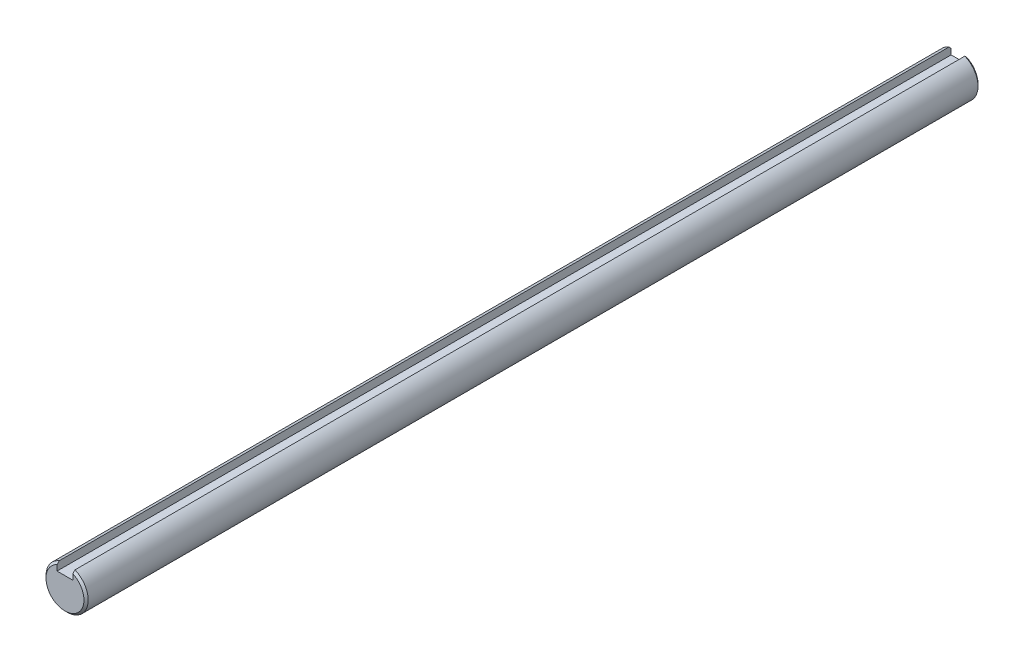
SolidWorks part; units mm, degrees
ref_plane "Front Plane" through (0, 0, 0) normal (0, 0, 1) x (1, 0, 0)
ref_plane "Top Plane" through (0, 0, 0) normal (0, 1, 0) x (1, 0, 0)
ref_plane "Right Plane" through (0, 0, 0) normal (1, 0, 0) x (0, 0, -1)
sketch "Sketch1" plane through (0, 0, 0) normal (0, 0, 1) x (1, 0, 0)
  line L0 (-2.2451, -2.2451) -> (-1.1225, -1.1225) construction
  line L1 (3.4925, 0) -> (-3.4925, 0) construction
  line L2 (0, 0) -> (0, 3.175) construction
  line L4 (-1.1906, 3.175) -> (1.1906, 3.175) construction
  line L5 (-1.1906, 3.175) -> (-1.1906, 1.7527) construction
  line L6 (-1.1906, 1.7527) -> (1.1906, 1.7527) construction
  line L7 (1.1906, 3.175) -> (1.1906, 1.7527) construction
  line L8 (-1.1906, 3.175) -> (1.1906, 1.7527) construction
  line L9 (-1.1906, 1.7527) -> (1.1906, 3.175) construction
  circle A0 centre (0, 0) radius 1.5875 construction
  circle A1 centre (0, 0) radius 3.175 construction
  point P6 (0, 2.4638)
  point P16 (-1.1906, 2.9433)
  dimension "Diameter" = 6.35
  dimension "Thread Dia" = 3.175
  dimension "D1" = 45
  dimension "Keyway Wd" = 2.3813
  dimension "Keyway Ht" = 1.1906
sketch "Sketch2" plane through (0, 0, 0) normal (1, 0, 0) x (0, 0, -1)
  line L0 (-67.31, -3.175) -> (67.31, -3.175) construction
  line L1 (0, 3.175) -> (0, -3.175) construction
  line L2 (0, 3.175) -> (0, -3.175) construction
  point P3 (54.61, -3.175)
  point P4 (-54.61, -3.175)
  dimension "Length" = 134.62
  dimension "D1" = 12.7
  dimension "D2" = 12.7
sketch "Sketch3" plane through (0, 0, 0) normal (0, 0, 1) x (1, 0, 0)
  circle A1 centre (0, 0) radius 3.175 construction
  circle A3 centre (0, 0) radius 3.175
extrude "Boss-Extrude2" add sketch "Sketch3" along normal up to vertex (67.31 mm away) and the other way up to vertex (67.31 mm away) up to point (0, -3.175, 67.31) other way up to point (0, -3.175, -67.31)
sketch "Sketch10" plane through (0, 0, 0) normal (0, 0, 1) x (1, 0, 0)
  line L1 (1.1906, 3.175) -> (1.1906, 1.7527) construction
  line L2 (-1.1906, 1.7527) -> (1.1906, 1.7527) construction
  line L3 (-1.1906, 3.175) -> (-1.1906, 1.7527) construction
  line L4 (-1.1906, 3.175) -> (1.1906, 3.175) construction
  line L5 (1.1906, 3.175) -> (1.1906, 1.7527)
  line L6 (-1.1906, 1.7527) -> (1.1906, 1.7527)
  line L7 (-1.1906, 3.175) -> (-1.1906, 1.7527)
  line L8 (-1.1906, 3.175) -> (1.1906, 3.175)
extrude "Cut-Extrude5" cut sketch "Sketch10" against normal through all both and the other way through all
chamfer "Chamfer1" distance 0.3175 angle 45 2 edges at (0, -3.175, 67.31) (0, -3.175, -67.31)
equation "\"D1@Chamfer1\"= \"Diameter@Sketch1\" / 20"
equation "\"D1@Sketch2\"=\"Diameter@Sketch1\"*2"
equation "\"D2@Sketch2\"=\"D1@Sketch2\""
